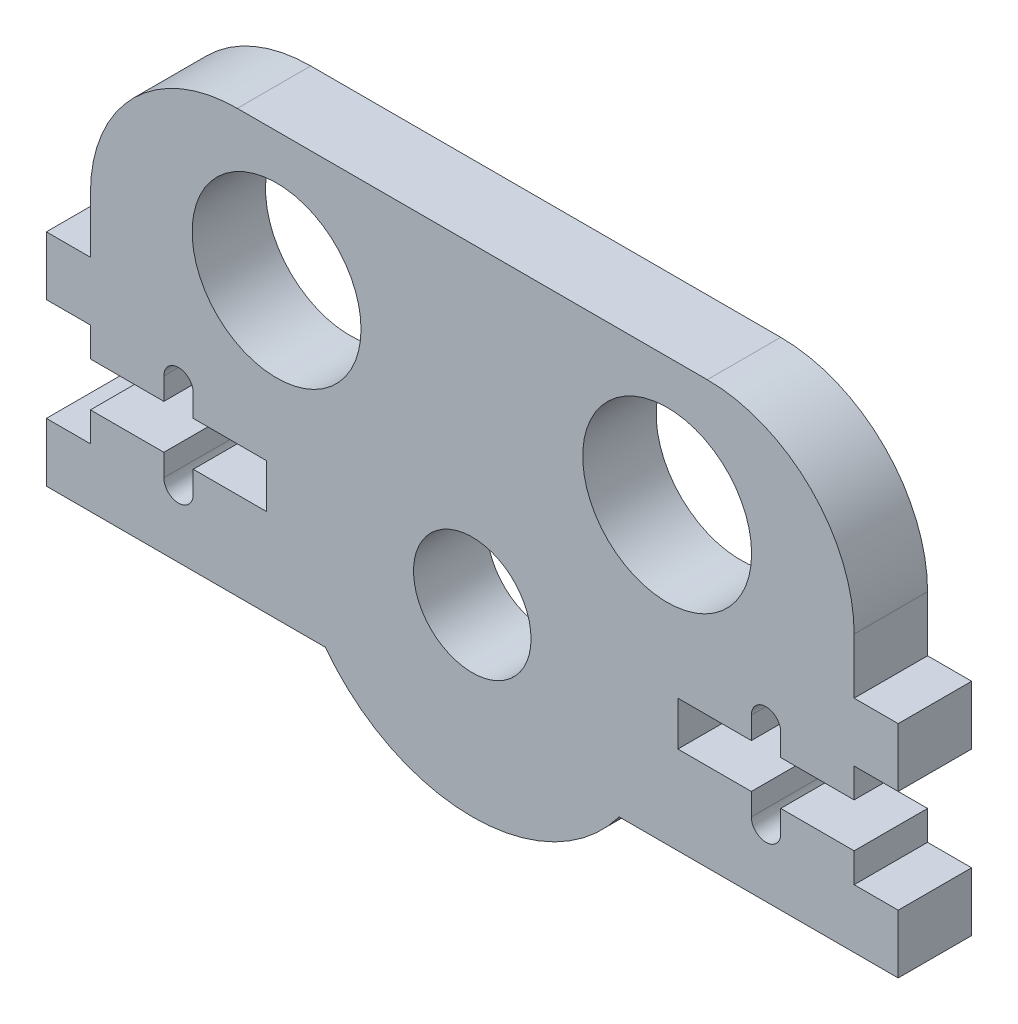
SolidWorks part; units mm, degrees
ref_plane "Front Plane" through (0, 0, 0) normal (0, 0, 1) x (1, 0, 0)
ref_plane "Top Plane" through (0, 0, 0) normal (0, 1, 0) x (1, 0, 0)
ref_plane "Right Plane" through (0, 0, 0) normal (1, 0, 0) x (0, 0, -1)
sketch "Sketch1" plane through (0, 0, 0) normal (0, 0, 1) x (1, 0, 0)
  line L0 (-20, 3) -> (-20, -3) construction
  line L1 (26, -7.5) -> (-26, -7.5)
  line L2 (26, -7.5) -> (26, 7.5)
  line L3 (26, 7.5) -> (-26, 7.5)
  line L4 (-26, -7.5) -> (-26, 7.5)
  line L5 (26, -7.5) -> (-26, 7.5) construction
  line L6 (26, 7.5) -> (-26, -7.5) construction
  line L7 (-14, -1.5) -> (-26, -1.5)
  line L8 (-14, -1.5) -> (-14, 1.5)
  line L9 (-14, 1.5) -> (-26, 1.5)
  line L10 (-26, -1.5) -> (-26, 1.5)
  line L11 (-14, -1.5) -> (-26, 1.5) construction
  line L12 (-14, 1.5) -> (-26, -1.5) construction
  line L13 (-19, 3) -> (-19, -3)
  line L14 (-21, 3) -> (-21, -3)
  line L15 (0, 7.5) -> (0, -7.5) construction
  line L16 (20, 3) -> (20, -3) construction
  line L17 (19, 3) -> (19, -3)
  line L18 (21, 3) -> (21, -3)
  line L19 (14, 1.5) -> (26, -1.5) construction
  line L20 (14, -1.5) -> (26, 1.5) construction
  line L21 (14, 1.5) -> (26, 1.5)
  line L22 (14, -1.5) -> (14, 1.5)
  line L23 (14, -1.5) -> (26, -1.5)
  circle A0 centre (0, 0) radius 12.5
  arc A1 (-19, 3) -> (-21, 3) centre (-20, 3) ccw
  arc A2 (-21, -3) -> (-19, -3) centre (-20, -3) ccw
  arc A3 (19, 3) -> (21, 3) centre (20, 3) cw
  arc A4 (21, -3) -> (19, -3) centre (20, -3) cw
  point P7 (-20, 0)
  point P14 (-20, 0)
  point P23 (20, 0)
  dimension "D1" = 25
  dimension "D2" = 52
  dimension "D3" = 3
  dimension "D4" = 12
  dimension "D5" = 2
  dimension "D6" = 8
  dimension "D7" = 15
extrude "Boss-Extrude1" add sketch "Sketch1" along normal blind 5 contours L3 A0 L1 | L3 A0 | L1 A0 | A2 L14 L7 L4 L1 A0 L3 L9 A1 L13 L8 | L18 A4 L17 L23 L22 L21 A3 L2 L3 A0 L1 region at (18, -7.2807, 0) region at (0, -9.5388, 0) region at (0, 0, 0) region at (-18, -7.2807, 0) region at (0, 9.5388, 0)
sketch "Sketch2" plane through (0, 0, 5) normal (0, 0, 1) x (1, 0, 0)
  circle A0 centre (0, 0) radius 4
  dimension "D1" = 8
extrude "Cut-Extrude1" cut sketch "Sketch2" against normal blind 5
sketch "Sketch3" plane through (0, 0, 5) normal (0, 0, 1) x (1, 0, 0)
  line L0 (26, 1.5) -> (26, 7.5) construction
  line L1 (-26, 7.5) -> (26, 7.5)
  line L2 (-26, 7.5) -> (-26, 11.2805)
  line L3 (-16, 21.2805) -> (16, 21.2805)
  line L4 (26, 7.5) -> (26, 11.2805)
  line L5 (-13.3258, 12.4694) -> (13.2683, 12.5305) construction
  line L6 (-1013.3258, 18.2805) -> (48986.6742, 18.2805) construction
  circle A0 centre (-13.3258, 12.4694) radius 5.75
  circle A1 centre (13.2683, 12.5305) radius 5.75
  arc A2 (10, 7.5) -> (-10, 7.5) centre (0, 0) ccw construction
  arc A3 (16, 21.2805) -> (26, 11.2805) centre (16, 11.2805) cw
  arc A4 (-16, 21.2805) -> (-26, 11.2805) centre (-16, 11.2805) ccw
  line M2 (26, 7.5) -> (10, 7.5)
  arc M3 (10, 7.5) -> (-10, 7.5) centre (0, 0) ccw
  line M4 (-10, 7.5) -> (-26, 7.5)
  dimension "D1" = 11.5
  dimension "D3" = 10
  dimension "D2" = 3
extrude "Boss-Extrude2" add sketch "Sketch3" against normal blind 5 contours L3 A4 L2 A0 A1 L4 A3 M4 M3 M2 | A0 M4 M3 | A1 M3 M2 region at (-9.9299, 7.7512, 5) region at (9.9366, 7.7605, 5) region at (0.0024, 15.6168, 5)
extrude "Cut-Extrude2" cut sketch "Sketch3<3>" against normal blind 10 contours A0 | A1
sketch "Sketch3<3>" plane through (0, 0, 5) normal (0, 0, 1) x (1, 0, 0) same geometry as "Sketch3"
sketch "Sketch4" plane through (0, 0, 5) normal (0, 0, 1) x (1, 0, 0)
  line L1 (-26, 3.5) -> (-29, 3.5)
  line L2 (-26, 3.5) -> (-26, 7.5)
  line L3 (-26, 7.5) -> (-29, 7.5)
  line L4 (-29, 3.5) -> (-29, 7.5)
  line L5 (-26, -7.5) -> (-29, -7.5)
  line L6 (-26, -7.5) -> (-26, -3.5)
  line L7 (-26, -3.5) -> (-29, -3.5)
  line L8 (-29, -7.5) -> (-29, -3.5)
  line L9 (-21, -1.5) -> (-26, -1.5) construction
  line L10 (-21, 1.5) -> (-26, 1.5) construction
  line L11 (-26, 1.5) -> (-26, 11.2805) construction
  dimension "D1" = 3
  dimension "D2" = 2
  dimension "D3" = 2
extrude "Boss-Extrude3" add sketch "Sketch4" against normal blind 5
mirror "Mirror1" about plane through (0, 0, 0) normal (1, 0, 0) of "Boss-Extrude3"
